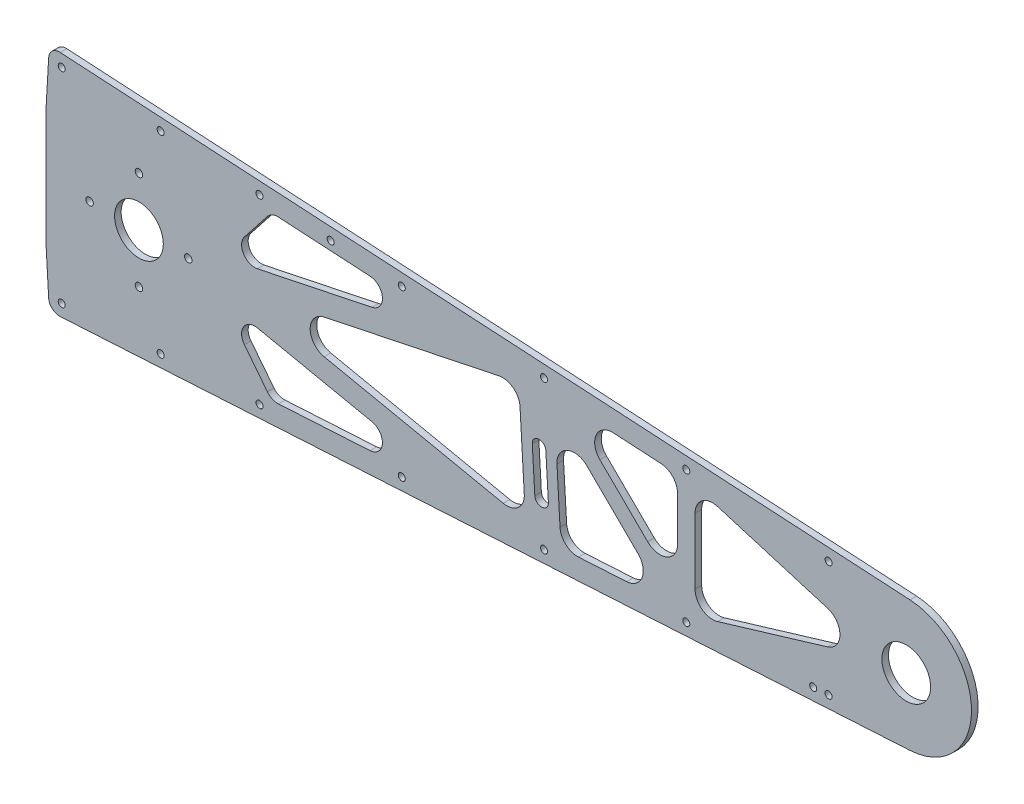
SolidWorks part; units mm, degrees
material "Thornel VCB-20 Carbon Cloth"
ref_plane "Front Plane" through (0, 0, 0) normal (0, 0, 1) x (1, 0, 0)
ref_plane "Top Plane" through (0, 0, 0) normal (0, 1, 0) x (1, 0, 0)
ref_plane "Right Plane" through (0, 0, 0) normal (1, 0, 0) x (0, 0, -1)
sketch "Sketch1" plane through (0, 0, 0) normal (0, 0, 1) x (1, 0, 0)
  line L0 (-175, 0) -> (175, 0) construction
  line L1 (-172.1122, 49.9165) -> (176.7203, 29.7354)
  line L2 (-172.1122, -49.9165) -> (176.7203, -29.7354)
  line L3 (139.566, 26.3757) -> (-120, 41.3925) construction
  line L4 (-55.1085, -37.6383) -> (9.783, -33.8841) construction
  line L5 (-125, 0) -> (-125, 62.9978) construction
  line L6 (-55.5713, 29.6383) -> (-120.4628, 33.3925) construction
  line L7 (-120.4628, 33.3925) -> (-120, 41.3925) construction
  line L8 (-55.5713, 29.6383) -> (-55.1085, 37.6383) construction
  line L9 (-88.0171, 31.5154) -> (-87.5543, 39.5154) construction
  line L10 (-120, -41.3925) -> (-165.1122, -44.0024) construction
  line L11 (139.566, -26.3757) -> (74.6745, -30.1299) construction
  circle A0 centre (175, 0) radius 11.1125
  arc A1 (176.7203, 29.7354) -> (176.7203, -29.7354) centre (175, 0) cw
  circle A3 centre (-175, 0) radius 22.5 construction
  circle A7 centre (-175, 0) radius 11.1125
  circle A9 centre (-120, 41.3925) radius 1.6
  circle A10 centre (-55.1085, 37.6383) radius 1.6
  circle A11 centre (9.783, 33.8841) radius 1.6
  circle A12 centre (74.6745, 30.1299) radius 1.6
  circle A13 centre (139.566, 26.3757) radius 1.6
  circle A15 centre (139.566, -26.3757) radius 1.6
  circle A16 centre (74.6745, -30.1299) radius 1.6
  circle A17 centre (9.783, -33.8841) radius 1.6
  circle A18 centre (-55.1085, -37.6383) radius 1.6
  circle A19 centre (-120, -41.3925) radius 1.6
  arc A20 (-172.1122, 49.9165) -> (-172.1122, -49.9165) centre (-175, 0) ccw
  circle A21 centre (-87.5543, 39.5154) radius 1.6
  circle A22 centre (-165.1122, -44.0024) radius 1.6
  circle A23 centre (-165.1122, 44.0024) radius 1.6
  circle A24 centre (132.5777, -26.78) radius 1.6
  point P4 (0, 0)
  point P18 (-175, 22.5)
  point P21 (-197.5, 0)
  point P22 (-175, -22.5)
  point P23 (-152.5, 0)
  point P30 (-88.0171, 31.5154)
  dimension "D2" = 22.225
  dimension "D3" = 50
  dimension "D5" = 45
  dimension "D6" = 3.2
  dimension "D7" = 260
  dimension "D8" = 5
  dimension "D9" = 7
  dimension "D10" = 22.225
  dimension "D11" = 7
  dimension "D16" = 5
  dimension "D1" = 350
  dimension "D4" = 8
  dimension "D12" = 5.5
extrude "Boss-Extrude1" add sketch "Sketch1" along normal blind 3
sketch "Sketch4" plane through (0, 0, 3) normal (0, 0, 1) x (1, 0, 0)
  point P10 (-197.5, 0)
  point P13 (-175, 22.5)
  point P16 (-152.5, 0)
  point P19 (-175, -22.5)
hole_wizard "M3 Clearance Hole1" positions "Sketch4" profile "Sketch6" hole size "M3" standard "ANSI Metric" end condition up to next
sketch "Sketch6" plane through (-197.5, 0, 3) normal (1, 0, 0) x (0, -1, 0)
  line L0 (0, 0) -> (0, 3)
  line L1 (0, 3) -> (1.7, 3)
  line L2 (1.7, 3) -> (1.7, 0)
  line L5 (1.7, 0) -> (0, 0)
  line L11 (0, -6.35) -> (0, 107.95) construction
  dimension "Thru Hole Dia." = 3.4
  dimension "Thru Hole Depth" = 3
sketch "Sketch7" plane through (0, 0, 3) normal (0, 0, 1) x (1, 0, 0)
  line L0 (74.6745, 30.1299) -> (74.6745, -30.1299) construction
  line L1 (74.6745, -30.1299) -> (175, 0) construction
  line L2 (175, 0) -> (74.6745, 30.1299) construction
  line L3 (175, 0) -> (-152.5, 0) construction
  line L4 (175, -29.8349) -> (175, 29.8349) construction
  line L5 (88.9755, 22.7026) -> (139.0575, 7.6619)
  line L6 (139.0575, -7.6619) -> (88.9755, -22.7026)
  line L7 (78.6745, -15.0407) -> (78.6745, 15.0407)
  line L8 (9.783, -33.8841) -> (5.5294, 39.6394) construction
  line L9 (9.783, 33.8841) -> (74.6745, -30.1299) construction
  line L10 (9.783, 33.8841) -> (74.6745, 30.1299) construction
  line L11 (9.783, -33.8841) -> (74.6745, -30.1299) construction
  line L12 (-152.5, 0) -> (-55.1085, 37.6383) construction
  line L13 (-55.1085, 37.6383) -> (9.783, 33.8841) construction
  line L14 (9.783, 33.8841) -> (-152.5, 0) construction
  line L15 (70.6745, -1.436) -> (70.6745, 18.8041)
  line L16 (63.1365, 26.7907) -> (41.3408, 28.0517)
  line L17 (35.2605, 14.3698) -> (57.0563, -7.1312)
  line L18 (29.2743, 9.0376) -> (52.6422, -14.0143)
  line L19 (47.486, -27.6962) -> (25.5253, -28.9667)
  line L20 (17.0766, -21.4421) -> (15.6694, 2.8804)
  line L21 (176.7203, 29.7354) -> (-172.1122, 49.9165) construction
  line L22 (-172.1122, -49.9165) -> (176.7203, -29.7354) construction
  line L23 (0.7692, -16.5921) -> (-1.1805, 17.1091)
  line L24 (-10.8023, 24.4781) -> (-90.5308, 7.8311)
  line L25 (-90.5308, -7.8311) -> (-8.8525, -24.8852)
  line L35 (-197.5, 0) -> (-55.1085, 37.6383) construction
  line L52 (-55.1085, -37.6383) -> (-175, -22.5) construction
  line L53 (-15.2425, -47.7117) -> (-52.5586, -43) construction
  line L54 (-0.7058, -39.4678) -> (2.1851, -39.8329) construction
  line L55 (8.6627, -14.5198) -> (7.5076, 5.4468) construction
  line L56 (5.5679, -14.6989) -> (4.4127, 5.2678)
  line L57 (11.7575, -14.3408) -> (10.6024, 5.6258)
  line L58 (176.7203, 29.7354) -> (-172.1122, 49.9165) construction
  line L59 (-175, 22.5) -> (-165.1122, 44.0024) construction
  line L60 (-152.5, 0) -> (-120, 41.3925) construction
  line L61 (-126.8967, 21.2738) -> (-116.4321, 34.6016)
  line L62 (-111.3663, 36.8863) -> (-69.5778, 34.4687)
  line L63 (-68.698, 22.6054) -> (-120.9512, 11.6951)
  line L64 (-165.9126, 32.6875) -> (-164.3288, 36.1317)
  line L65 (-158.531, 39.6149) -> (-142.9867, 38.7156)
  line L66 (-138.6141, 29.0203) -> (-146.1029, 19.4825)
  line L67 (-175.7645, 30.4115) -> (-175.2558, 31.5179)
  line L68 (-197.5, 0) -> (-225, 0) construction
  line L69 (-208.0189, 4) -> (-206.9726, 4)
  line L70 (-208.0189, -4) -> (-206.9726, -4)
  line L71 (-175.7645, -30.4115) -> (-175.2558, -31.5179)
  line L72 (-165.9126, -32.6875) -> (-164.3288, -36.1317)
  line L73 (-158.531, -39.6149) -> (-142.9867, -38.7156)
  line L74 (-138.6141, -29.0203) -> (-146.1029, -19.4825)
  line L75 (-111.3663, -36.8863) -> (-69.5778, -34.4687)
  line L76 (-126.8967, -21.2738) -> (-116.4321, -34.6016)
  line L77 (-68.698, -22.6054) -> (-120.9512, -11.6951)
  arc A0 (139.0575, 7.6619) -> (139.0575, -7.6619) centre (136.7565, 0) cw
  arc A1 (88.9755, -22.7026) -> (78.6745, -15.0407) centre (86.6745, -15.0407) cw
  arc A2 (88.9755, 22.7026) -> (78.6745, 15.0407) centre (86.6745, 15.0407) ccw
  arc A3 (70.6745, 18.8041) -> (63.1365, 26.7907) centre (62.6745, 18.8041) ccw
  arc A4 (41.3408, 28.0517) -> (35.2605, 14.3698) centre (40.8787, 20.065) ccw
  arc A5 (70.6745, -1.436) -> (57.0563, -7.1312) centre (62.6745, -1.436) cw
  arc A6 (52.6422, -14.0143) -> (47.486, -27.6962) centre (47.024, -19.7095) cw
  arc A7 (25.5253, -28.9667) -> (17.0766, -21.4421) centre (25.0632, -20.98) cw
  arc A8 (29.2743, 9.0376) -> (15.6694, 2.8804) centre (23.6561, 3.3424) ccw
  arc A9 (0.7692, -16.5921) -> (-8.8525, -24.8852) centre (-7.2174, -17.0541) cw
  arc A10 (-1.1805, 17.1091) -> (-10.8023, 24.4781) centre (-9.1672, 16.647) ccw
  arc A11 (-90.5308, 7.8311) -> (-90.5308, -7.8311) centre (-88.8957, 0) ccw
  circle A30 centre (-175, 0) radius 11.1125 construction
  circle A31 centre (-175, 0) radius 11.1125 construction
  circle A32 centre (-175, 0) radius 22.5 construction
  circle A49 centre (9.783, -33.8841) radius 1.6 construction
  circle A50 centre (9.783, -33.8841) radius 1.6
  circle A52 centre (175, 0) radius 11.1125 construction
  circle A53 centre (175, 0) radius 11.1125 construction
  arc A56 (5.5679, -14.6989) -> (11.7575, -14.3408) centre (8.6627, -14.5198) ccw
  arc A57 (10.6024, 5.6258) -> (4.4127, 5.2678) centre (7.5076, 5.4468) ccw
  circle A58 centre (-165.1122, 44.0024) radius 1.6 construction
  circle A60 centre (-120, 41.3925) radius 1.6 construction
  arc A61 (-155.1524, 19.0348) -> (-163.0653, 24.7753) centre (-175, 0) ccw
  arc A62 (-180.1025, 27.0225) -> (-201.2462, 8.209) centre (-175, 0) ccw
  arc A63 (-181.6995, 39.942) -> (-213.7614, 11.7391) centre (-175, 0) ccw
  arc A64 (-172.1122, 49.9165) -> (-172.1122, -49.9165) centre (-175, 0) ccw construction
  arc A65 (-175.2558, 31.5179) -> (-181.6995, 39.942) centre (-180.707, 34.0247) ccw
  arc A66 (-213.7614, 11.7391) -> (-208.0189, 4) centre (-208.0189, 10) ccw
  arc A67 (-201.2462, 8.209) -> (-206.9726, 4) centre (-206.9726, 10) cw
  arc A68 (-180.1025, 27.0225) -> (-175.7645, 30.4115) centre (-181.2158, 32.9183) ccw
  arc A69 (-69.5778, 34.4687) -> (-68.698, 22.6054) centre (-69.9244, 28.4787) cw
  arc A70 (-116.4321, 34.6016) -> (-111.3663, 36.8863) centre (-111.7129, 30.8963) cw
  arc A71 (-126.8967, 21.2738) -> (-120.9512, 11.6951) centre (-122.1775, 17.5685) ccw
  arc A72 (-142.9867, 38.7156) -> (-138.6141, 29.0203) centre (-143.3332, 32.7257) cw
  arc A73 (-164.3288, 36.1317) -> (-158.531, 39.6149) centre (-158.8776, 33.625) cw
  arc A74 (-163.0653, 24.7753) -> (-165.9126, 32.6875) centre (-160.4614, 30.1808) cw
  arc A75 (-155.1524, 19.0348) -> (-146.1029, 19.4825) centre (-150.822, 23.1878) ccw
  arc A76 (-213.7614, -11.7391) -> (-208.0189, -4) centre (-208.0189, -10) cw
  arc A77 (-201.2462, -8.209) -> (-206.9726, -4) centre (-206.9726, -10) ccw
  arc A78 (-180.1025, -27.0225) -> (-201.2462, -8.209) centre (-175, 0) cw
  arc A79 (-181.6995, -39.942) -> (-213.7614, -11.7391) centre (-175, 0) cw
  arc A80 (-180.1025, -27.0225) -> (-175.7645, -30.4115) centre (-181.2158, -32.9183) cw
  arc A81 (-175.2558, -31.5179) -> (-181.6995, -39.942) centre (-180.707, -34.0247) cw
  arc A82 (-164.3288, -36.1317) -> (-158.531, -39.6149) centre (-158.8776, -33.625) ccw
  arc A83 (-163.0653, -24.7753) -> (-165.9126, -32.6875) centre (-160.4614, -30.1808) ccw
  arc A84 (-155.1524, -19.0348) -> (-163.0653, -24.7753) centre (-175, 0) cw
  arc A85 (-155.1524, -19.0348) -> (-146.1029, -19.4825) centre (-150.822, -23.1878) cw
  arc A86 (-142.9867, -38.7156) -> (-138.6141, -29.0203) centre (-143.3332, -32.7257) ccw
  arc A87 (-69.5778, -34.4687) -> (-68.698, -22.6054) centre (-69.9244, -28.4787) ccw
  arc A88 (-116.4321, -34.6016) -> (-111.3663, -36.8863) centre (-111.7129, -30.8963) ccw
  arc A89 (-126.8967, -21.2738) -> (-120.9512, -11.6951) centre (-122.1775, -17.5685) cw
  point P36 (164.5699, 0)
  point P59 (-128.0368, 0)
  point P102 (-15.2425, -47.7117)
  point P126 (8.0851, -4.5365)
  dimension "D8" = 8
  dimension "D11" = 27.5
  dimension "D12" = 5
  dimension "D20" = 3.1
  dimension "D10" = 7
  dimension "D17" = 6
  dimension "D1" = 3
  dimension "D3" = 8
  dimension "D4" = 8
  dimension "D5" = 8
  dimension "D6" = 16
  dimension "D7" = 10
  dimension "D9" = 8
  dimension "D13" = 8
  dimension "D14" = 5
  dimension "D15" = 8
  dimension "D16" = 24.8967
  dimension "D22" = 20
extrude "Cut-Extrude1" cut sketch "Sketch7" against normal blind 10 contours L57 A57 L56 A56 | L24 A11 L25 A9 L23 A10 | L18 A8 L20 A7 L19 A6 | A89 L76 A88 L75 A87 L77 | L61 A71 L63 A69 L62 A70 | L20 A8 L18 A6 L19 A7 | L17 A5 L15 A3 L16 A4 | L7 A2 L5 A0 L6 A1 | L75 A87 L77 A89 L76 A88 region at (32.1755, -11.823, 3) region at (-38.9372, -0.1884, 3) region at (8.0851, -4.5365, 3) region at (-98.2756, 25.5667, 3) region at (-98.2756, -25.5667, 3)
sketch "Sketch9" [suppressed] plane through (0, 0, 3) normal (0, 0, 1) x (1, 0, 0)
  line L2 (176.7203, 29.7354) -> (-172.1122, 49.9165) construction
  line L3 (-172.1122, -49.9165) -> (176.7203, -29.7354) construction
  line L4 (254.5375, 0) -> (208, 0) construction
  line L5 (200.557, 2) -> (203.931, 2)
  line L6 (200.557, -2) -> (203.931, -2)
  line L7 (162.9445, 26.3755) -> (155.7345, 26.7926)
  line L8 (162.9445, -26.3755) -> (155.7345, -26.7926)
  arc A1 (155.7345, -26.7926) -> (155.7345, 26.7926) centre (175, 0) ccw
  arc A2 (176.7203, -29.7354) -> (176.7203, 29.7354) centre (175, 0) ccw construction
  arc A3 (200.557, -2) -> (200.557, 2) centre (175, 0) ccw
  arc A4 (162.9445, 26.3755) -> (203.931, 2) centre (175, 0) cw
  arc A5 (203.931, -2) -> (162.9445, -26.3755) centre (175, 0) cw
  dimension "D1" = 33
  dimension "D2" = 4
  dimension "D3" = 4
extrude "Boss-Extrude2" [suppressed] add sketch "Sketch9" against normal up to surface (3 mm away) up to face at (-102.0595, -26.743, 0)
fillet "Fillet1" [suppressed] radius 1
fillet "Fillet2" [suppressed] radius 80
sketch "Sketch10" plane through (0, 0, 3) normal (0, 0, 1) x (1, 0, 0)
  line L0 (-165.1122, 44.0024) -> (-120, 41.3925) construction
  line L1 (-165.1122, 44.0024) -> (-210.2243, 46.6123) construction
  line L2 (-172.1122, 49.9165) -> (-210.905, 52.1608)
  line L3 (176.7203, 29.7354) -> (-172.1122, 49.9165) construction
  line L4 (-216.1854, 47.458) -> (-217.3977, 26.5035)
  line L5 (-172.1122, 49.9165) -> (-217.3977, 26.5035)
  circle A0 centre (-120, 41.3925) radius 1.6 construction
  circle A1 centre (-165.1122, 44.0024) radius 1.6 construction
  circle A2 centre (-210.2243, 46.6123) radius 1.6
  arc A3 (-172.1122, 49.9165) -> (-172.1122, -49.9165) centre (-175, 0) ccw construction
  arc A4 (-210.905, 52.1608) -> (-216.1854, 47.458) centre (-211.1938, 47.1692) ccw
  dimension "D2" = 5
  dimension "D1" = 6
extrude "Boss-Extrude3" add sketch "Sketch10" against normal up to surface (3 mm away) up to face at (-102.0595, -26.743, 0)
mirror "Mirror1" about plane through (0, 0, 0) normal (0, 1, 0) of "Boss-Extrude3"
sketch "Sketch11" plane through (0, 0, 0) normal (0, 0, -1) x (-1, 0, 0)
  line L0 (217.3977, -26.5035) -> (217.3977, 26.5035)
  arc A0 (217.3977, -26.5035) -> (217.3977, 26.5035) centre (175, 0) ccw construction
  arc A1 (217.3977, -26.5035) -> (217.3977, 26.5035) centre (175, 0) ccw
extrude "Cut-Extrude2" cut sketch "Sketch11" against normal through all both and the other way through all
